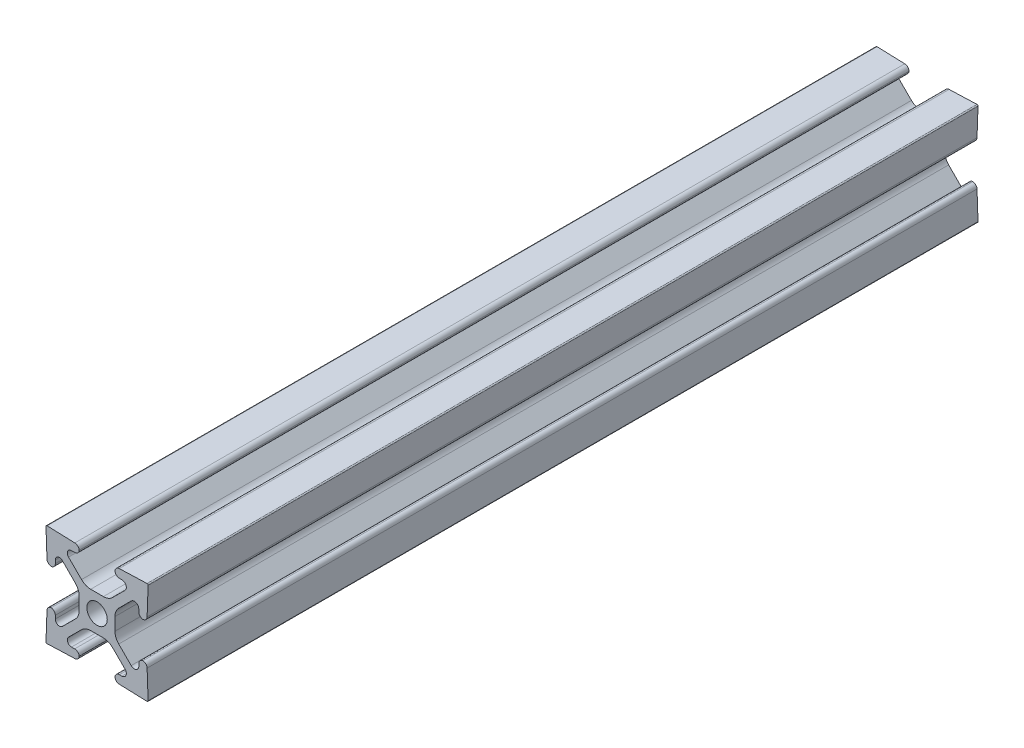
SolidWorks part; units mm, degrees
ref_plane "Front Plane" through (0, 0, 0) normal (0, 0, 1) x (1, 0, 0)
ref_plane "Top Plane" through (0, 0, 0) normal (0, 1, 0) x (1, 0, 0)
ref_plane "Right Plane" through (0, 0, 0) normal (1, 0, 0) x (0, 0, -1)
sketch "Sketch1" plane through (0, 0, 0) normal (0, 0, 1) x (1, 0, 0)
  line L5 (-8.7148, 10.2235) -> (-4.3815, 10.2235)
  line L6 (-10.2235, 4.3815) -> (-12.2257, 4.3815)
  line L19 (-4.3815, 10.2235) -> (-4.3815, 12.2257)
  line L20 (12.5095, 12.5095) -> (4.3815, 12.2257)
  line L21 (12.5095, 12.5095) -> (12.2257, 4.3815)
  line L22 (4.3815, 10.2235) -> (4.3815, 12.2257)
  line L23 (4.3815, 10.2235) -> (8.7148, 10.2235)
  line L24 (2.8728, 4.3815) -> (8.7148, 10.2235)
  line L25 (2.8728, 4.3815) -> (4.3815, 4.3815)
  line L26 (-2.8728, 4.3815) -> (-8.7148, 10.2235)
  line L27 (-12.5095, 12.5095) -> (-12.2257, 4.3815)
  line L28 (-12.5095, 12.5095) -> (-4.3815, 12.2257)
  line L29 (-10.2235, 4.3815) -> (-10.2235, 8.7148)
  line L31 (-4.3815, 2.8728) -> (-4.3815, 4.3815)
  line L32 (-4.3815, 4.3815) -> (-2.8728, 4.3815)
  line L42 (4.3815, 4.3815) -> (4.3815, 2.8728)
  line L43 (4.3815, 2.8728) -> (10.2235, 8.7148)
  line L44 (10.2235, 8.7148) -> (10.2235, 4.3815)
  line L45 (10.2235, 4.3815) -> (12.2257, 4.3815)
  line L46 (12.5095, -12.5095) -> (12.2257, -4.3815)
  line L47 (12.5095, -12.5095) -> (4.3815, -12.2257)
  line L48 (10.2235, -4.3815) -> (12.2257, -4.3815)
  line L50 (-4.3815, 2.8728) -> (-10.2235, 8.7148)
  line L51 (10.2235, -4.3815) -> (10.2235, -8.7148)
  line L52 (4.3815, -2.8728) -> (10.2235, -8.7148)
  line L53 (4.3815, -2.8728) -> (4.3815, -4.3815)
  line L54 (4.3815, -4.3815) -> (2.8728, -4.3815)
  line L55 (2.8728, -4.3815) -> (8.7148, -10.2235)
  line L56 (8.7148, -10.2235) -> (4.3815, -10.2235)
  line L57 (4.3815, -10.2235) -> (4.3815, -12.2257)
  line L58 (-12.5095, -12.5095) -> (-4.3815, -12.2257)
  line L59 (-12.5095, -12.5095) -> (-12.2257, -4.3815)
  line L60 (-4.3815, -10.2235) -> (-4.3815, -12.2257)
  line L61 (-4.3815, -10.2235) -> (-8.7148, -10.2235)
  line L62 (-2.8728, -4.3815) -> (-8.7148, -10.2235)
  line L63 (-2.8728, -4.3815) -> (-4.3815, -4.3815)
  line L64 (-4.3815, -4.3815) -> (-4.3815, -2.8728)
  line L65 (-4.3815, -2.8728) -> (-10.2235, -8.7148)
  line L66 (-10.2235, -8.7148) -> (-10.2235, -4.3815)
  line L67 (-10.2235, -4.3815) -> (-12.2257, -4.3815)
  point P25 (0, 0)
  point P42 (0, 0)
  dimension "D7" = 5.842
  dimension "D1" = 4
extrude "Boss-Extrude1" add sketch "Sketch1" along normal blind 203.2254
fillet "Fillet1" radius 1.0922 2 edges at (-4.3815, 10.2235, 101.6127) (-4.3815, 12.2257, 101.6127)
fillet "Fillet2" radius 1.0922 2 edges at (-10.2235, 4.3815, 101.6127) (-12.2257, 4.3815, 101.6127)
fillet "Fillet3" radius 1.016 1 edges at (-10.2235, 8.7148, 101.6127)
fillet "Fillet4" radius 1.016 1 edges at (-8.7148, 10.2235, 101.6127)
fillet "Fillet5" radius 0.254 1 edges at (-12.5095, 12.5095, 101.6127)
fillet "Fillet6" radius 0.254 1 edges at (-12.5095, -12.5095, 101.6127)
fillet "Fillet7" radius 0.254 1 edges at (12.5095, 12.5095, 101.6127)
fillet "Fillet8" radius 0.254 1 edges at (12.5095, -12.5095, 101.6127)
fillet "Fillet9" radius 1.016 2 edges at (-10.2235, -8.7148, 101.6127) (-8.7148, -10.2235, 101.6127)
fillet "Fillet10" radius 1.0922 4 edges at (-4.3815, -10.2235, 101.6127) (-4.3815, -12.2257, 101.6127) (-10.2235, -4.3815, 101.6127) (-12.2257, -4.3815, 101.6127)
fillet "Fillet11" radius 1.0922 4 edges at (4.3815, 10.2235, 101.6127) (4.3815, 12.2257, 101.6127) (10.2235, 4.3815, 101.6127) (12.2257, 4.3815, 101.6127)
fillet "Fillet12" radius 1.0922 4 edges at (12.2257, -4.3815, 101.6127) (10.2235, -4.3815, 101.6127) (4.3815, -12.2257, 101.6127) (4.3815, -10.2235, 101.6127)
fillet "Fillet13" radius 1.0922 2 edges at (8.7148, -10.2235, 101.6127) (10.2235, -8.7148, 101.6127)
fillet "Fillet14" radius 1.0922 2 edges at (8.7148, 10.2235, 101.6127) (10.2235, 8.7148, 101.6127)
sketch "Sketch2" plane through (0, 0, 203.2254) normal (0, 0, 1) x (1, 0, 0)
  line L1 (-4.3815, -4.3815) -> (4.3815, -4.3815)
  line L2 (-4.3815, -4.3815) -> (-4.3815, 4.3815)
  line L3 (-4.3815, 4.3815) -> (4.3815, 4.3815)
  line L4 (4.3815, -4.3815) -> (4.3815, 4.3815)
  line L5 (-4.3815, -4.3815) -> (4.3815, 4.3815) construction
  line L6 (-4.3815, 4.3815) -> (4.3815, -4.3815) construction
  circle A0 centre (0, 0) radius 2.5019
  point P0 (0, 0)
extrude "Boss-Extrude2" add sketch "Sketch2" against normal blind 203.2254
fillet "Fillet15" radius 3.175 8 edges at (2.8728, 4.3815, 101.6127) (-2.8728, 4.3815, 101.6127) (4.3815, -2.8728, 101.6127) (4.3815, 2.8728, 101.6127) (2.8728, -4.3815, 101.6127) (-2.8728, -4.3815, 101.6127) (-4.3815, 2.8728, 101.6127) (-4.3815, -2.8728, 101.6127)
